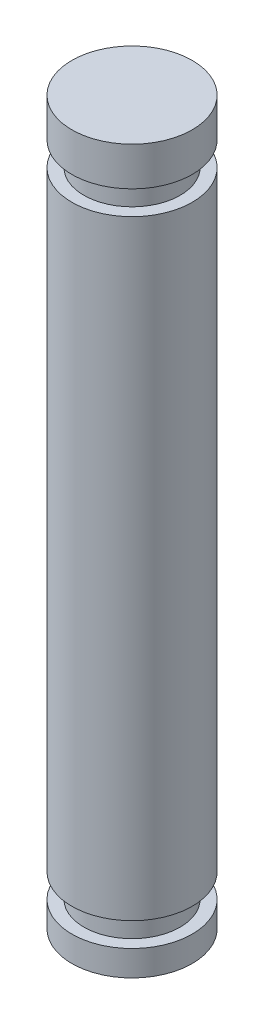
SolidWorks part; units mm, degrees
material "1060 Alloy"
ref_plane "Front Plane" through (0, 0, 0) normal (0, 0, 1) x (1, 0, 0)
ref_plane "Top Plane" through (0, 0, 0) normal (0, 1, 0) x (1, 0, 0)
ref_plane "Right Plane" through (0, 0, 0) normal (1, 0, 0) x (0, 0, -1)
sketch "Sketch3" plane through (0, 0, 0) normal (1, 0, 0) x (0, 0, -1)
  line L1 (0, 0) -> (10, 0)
  line L2 (0, 0) -> (0, 120)
  line L3 (0, 120) -> (10, 120)
  line L4 (10, 0) -> (10, 120)
  line L5 (10, 4.2435) -> (8, 4.2435)
  line L6 (10, 4.2435) -> (10, 8.2435)
  line L7 (10, 8.2435) -> (8, 8.2435)
  line L8 (8, 4.2435) -> (8, 8.2435)
  line L9 (10, 113.5686) -> (8, 113.5686)
  line L10 (10, 113.5686) -> (10, 109.5686)
  line L11 (10, 109.5686) -> (8, 109.5686)
  line L12 (8, 113.5686) -> (8, 109.5686)
  dimension "D1" = 120
  dimension "D2" = 10
  dimension "D3" = 2
  dimension "D4" = 4
revolve "Revolve1" add sketch "Sketch3" angle 360 about L2 region at (0, 60.0148, -4.9459)
